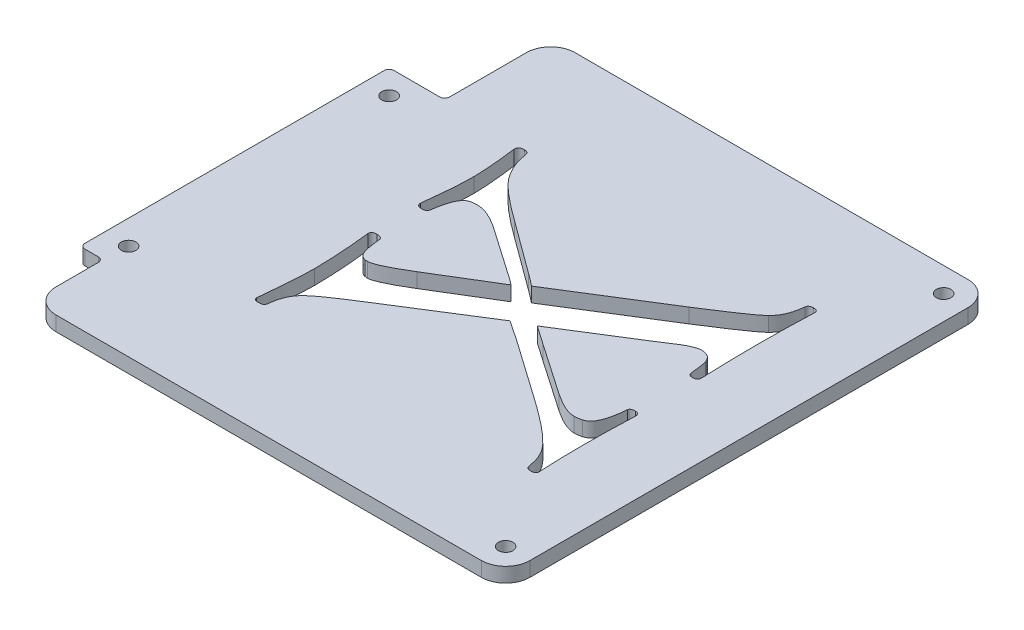
SolidWorks part; units mm, degrees
ref_plane "Front Plane" through (0, 0, 0) normal (0, 0, 1) x (1, 0, 0)
ref_plane "Top Plane" through (0, 0, 0) normal (0, 1, 0) x (1, 0, 0)
ref_plane "Right Plane" through (0, 0, 0) normal (1, 0, 0) x (0, 0, -1)
ref_plane "Plane1" through (0, 23, 0) normal (0, 1, 0) x (1, 0, 0)
sketch "Sketch1" plane through (0, 23, 0) normal (0, 1, 0) x (1, 0, 0)
  line L0 (98.3054, 50) -> (98.3054, 28.2195)
  line L1 (189.0458, 50) -> (98.3054, 50)
  line L2 (189.0458, 50) -> (189.0458, -50)
  line L3 (189.0458, -50) -> (97.6502, -50)
  line L5 (98.3054, 28.2195) -> (86.88, 28.2195)
  line L6 (86.88, 28.2195) -> (86.88, -35.308)
  line L7 (86.88, -35.308) -> (91.6598, -35.308)
  line L8 (91.6598, -35.308) -> (91.6598, -50)
  line L9 (91.6598, -50) -> (97.6502, -50)
  line L10 (94.8054, 33.2195) -> (98.3054, 33.2195) construction
  line L11 (184.0458, 45) -> (184.0458, 50) construction
  line L12 (93.3054, 31.7195) -> (93.3054, 28.2195) construction
  line L13 (99.4745, -35.308) -> (86.1225, -35.308) construction
  line L14 (88.1598, -40.308) -> (91.6598, -40.308) construction
  line L15 (86.6598, -38.808) -> (86.6598, -35.308) construction
  line L16 (189.0458, 0) -> (190, 0) construction
  line L17 (190, -60) -> (190, 60) construction
  line L18 (105.0183, -40) -> (185.0183, -40) construction
  line L19 (105.0183, -40) -> (105.0183, 40) construction
  line L20 (105.0183, 40) -> (185.0183, 40) construction
  line L21 (185.0183, -40) -> (185.0183, 40) construction
  line L22 (184.0458, 45) -> (189.0458, 45) construction
  line L23 (184.0458, -45) -> (189.0458, -45) construction
  line L24 (184.0458, -45) -> (184.0458, -50) construction
  line L25 (91.88, 23.2195) -> (91.88, 28.2195) construction
  line L26 (91.88, 23.2195) -> (86.88, 23.2195) construction
  line L27 (91.88, -30.308) -> (91.88, -35.308) construction
  line L28 (91.88, -30.308) -> (86.88, -30.308) construction
  circle A0 centre (86.6598, -40.308) radius 1.5 construction
  circle A1 centre (93.3054, 33.2195) radius 1.5 construction
  circle A2 centre (184.0458, 45) radius 1.5 construction
  circle A3 centre (184.0458, 45) radius 1.5 construction
  circle A4 centre (184.0458, -45) radius 1.5 construction
  circle A6 centre (91.88, 23.2195) radius 1.5 construction
  circle A7 centre (91.88, -30.308) radius 1.5 construction
  point P32 (185.0183, 0)
  dimension "D1" = 100
  dimension "D2" = 80
  dimension "D3" = 3.5
  dimension "D4" = 5
extrude "Boss-Extrude1" add sketch "Sketch1" along normal blind 3
fillet "Fillet3" radius 5 4 edges at (189.0458, 24.5, -50) (98.3054, 24.5, -50) (91.6598, 24.5, 50) (189.0458, 24.5, 50)
fillet "Fillet2" radius 1 4 edges at (86.88, 24.5, -28.2195) (98.3054, 24.5, -28.2195) (91.6598, 24.5, 35.308) (86.88, 24.5, 35.308)
sketch "Sketch2" plane through (0, 23, 0) normal (0, 1, 0) x (1, 0, 0)
  circle A0 centre (184.0458, -45) radius 1.5 construction
  circle A1 centre (184.0458, -45) radius 1.5
  circle A2 centre (91.88, -30.308) radius 1.5 construction
  circle A3 centre (91.88, -30.308) radius 1.5
  circle A4 centre (91.88, 23.2195) radius 1.5 construction
  circle A5 centre (91.88, 23.2195) radius 1.5
  circle A6 centre (184.0458, 45) radius 1.5 construction
  circle A7 centre (184.0458, 45) radius 1.5
extrude "Cut-Extrude1" cut sketch "Sketch2" along normal up to surface (3 mm away) up to face at (116.4727, 26, 1.7721)
sketch "Sketch4" plane through (0, 23, 0) normal (0, 1, 0) x (1, 0, 0)
  line L0 (176.5151, -28.0588) -> (176.5151, 28.0588) construction
  line L2 (150, 0) -> (182, 0) construction
  text T0 "X" font "@Yu Mincho Demibold" height 60
  point P3 (176.5151, 0)
extrude "Cut-Extrude2" cut sketch "Sketch4" along normal up to surface (3 mm away) up to face at (184.0458, 26, 43.5)
